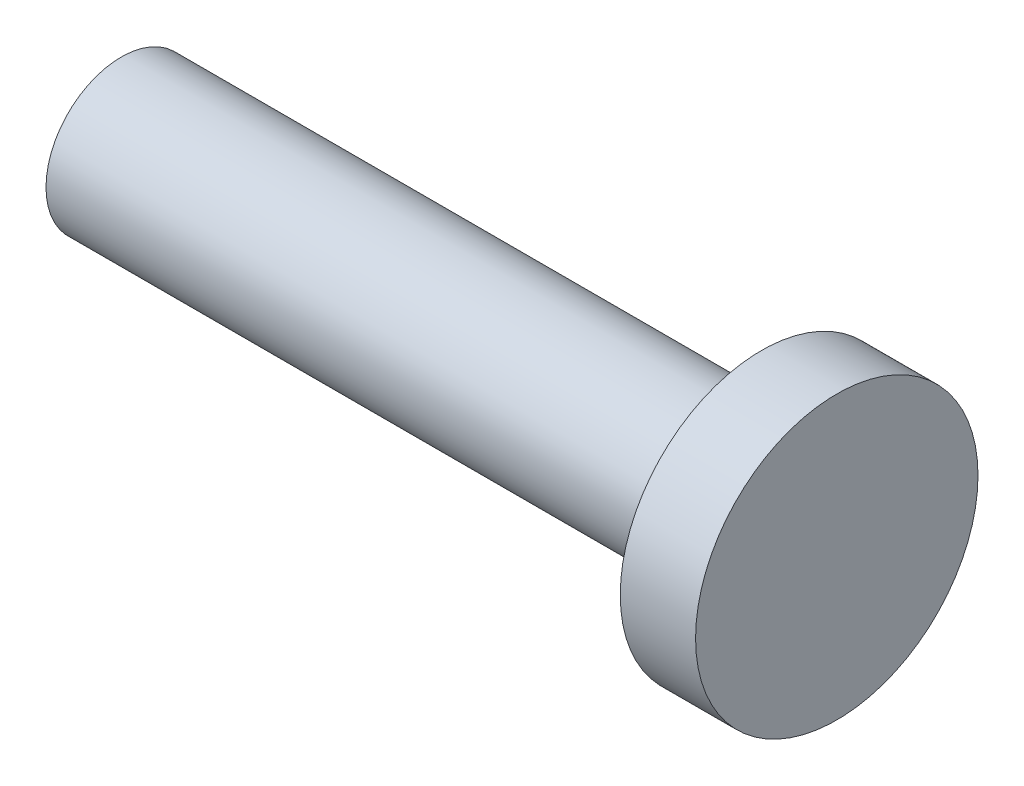
SolidWorks part; units mm, degrees
ref_plane "Front Plane" through (0, 0, 0) normal (0, 0, 1) x (1, 0, 0)
ref_plane "Top Plane" through (0, 0, 0) normal (0, 1, 0) x (1, 0, 0)
ref_plane "Right Plane" through (0, 0, 0) normal (1, 0, 0) x (0, 0, -1)
sketch "Sketch1" plane through (0, 0, 0) normal (0, 0, 1) x (1, 0, 0)
  line L0 (-150.2274, 0) -> (-141.7274, 0)
  line L1 (-141.7274, 0) -> (-141.7274, 1)
  line L2 (-141.7274, 1) -> (-150.2274, 1)
  line L3 (-150.2274, 1) -> (-150.2274, 0)
  dimension "6" = 8.5
  dimension "D2" = 1
revolve "Revolve1" add sketch "Sketch1" angle 360 about L0
sketch "Sketch2" plane through (-141.7274, 0, 0) normal (1, 0, 0) x (0, 0, -1)
  circle A0 centre (0, 0) radius 1.875
  dimension "D1" = 3.75
extrude "Boss-Extrude1" add sketch "Sketch2" along normal blind 1
